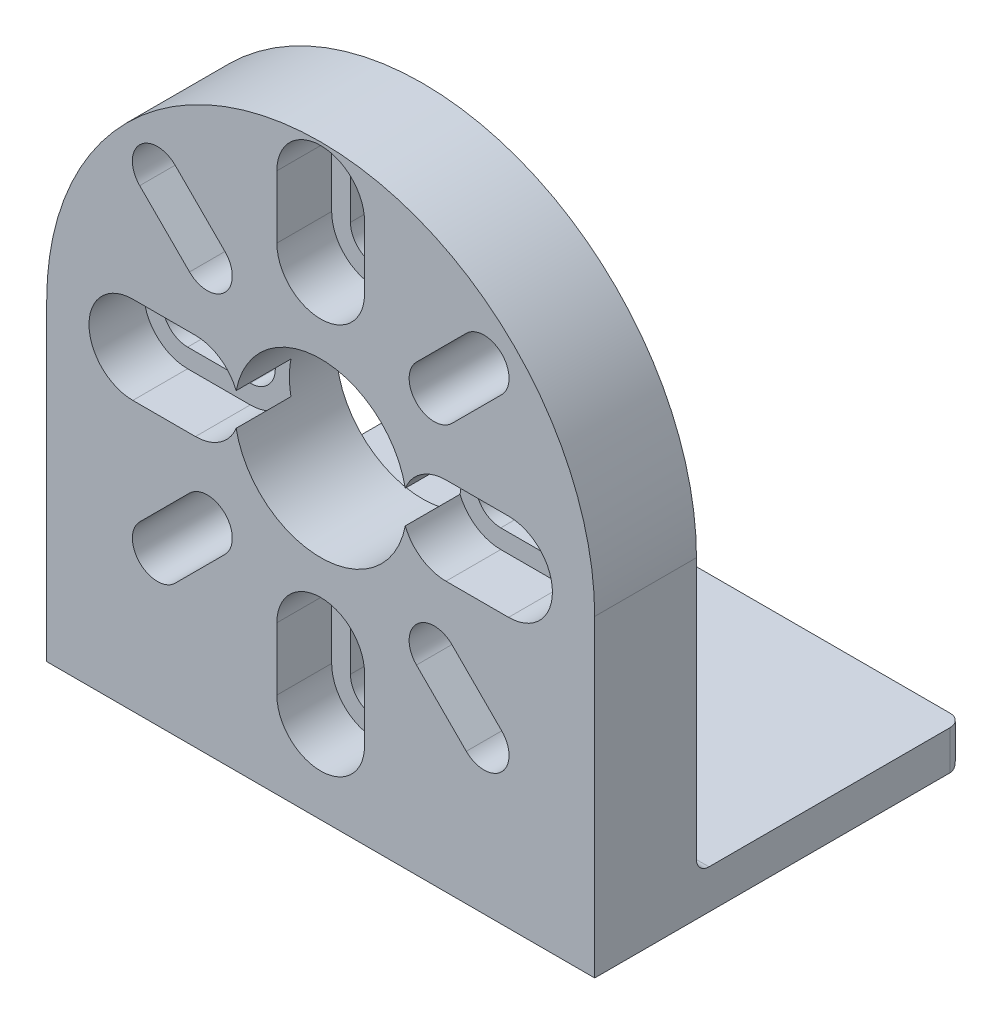
SolidWorks part; units mm, degrees
ref_plane "前视基准面" through (0, 0, 0) normal (0, 0, 1) x (1, 0, 0)
ref_plane "上视基准面" through (0, 0, 0) normal (0, 1, 0) x (1, 0, 0)
ref_plane "右视基准面" through (0, 0, 0) normal (1, 0, 0) x (0, 0, -1)
sketch "草图1" plane through (0, 0, 0) normal (0, 0, 1) x (1, 0, 0)
  line L0 (0, 0) -> (0, 8.1405) construction
  line L1 (0, 14.5) -> (0, 10.5) construction
  line L2 (6.9459, 0) -> (-5.9734, 0) construction
  line L3 (1.6, 14.5) -> (1.6, 10.5)
  line L4 (-1.6, 14.5) -> (-1.6, 10.5)
  line L5 (0, -14.5) -> (0, -10.5) construction
  line L6 (1.6, -14.5) -> (1.6, -10.5)
  line L7 (-1.6, -14.5) -> (-1.6, -10.5)
  line L8 (-12, 0) -> (-8, 0) construction
  line L11 (-12, 1.6) -> (-8, 1.6)
  line L14 (-12, -1.6) -> (-8, -1.6)
  line L15 (12, 0) -> (8, 0) construction
  line L16 (12, 1.6) -> (8, 1.6)
  line L17 (12, -1.6) -> (8, -1.6)
  arc A0 (1.6, 14.5) -> (-1.6, 14.5) centre (0, 14.5) ccw
  arc A1 (-1.6, 10.5) -> (1.6, 10.5) centre (0, 10.5) ccw
  arc A2 (1.6, -14.5) -> (-1.6, -14.5) centre (0, -14.5) cw
  arc A3 (-1.6, -10.5) -> (1.6, -10.5) centre (0, -10.5) cw
  arc A8 (-12, 1.6) -> (-12, -1.6) centre (-12, 0) ccw
  arc A9 (-8, -1.6) -> (-8, 1.6) centre (-8, 0) ccw
  arc A10 (12, 1.6) -> (12, -1.6) centre (12, 0) cw
  arc A11 (8, -1.6) -> (8, 1.6) centre (8, 0) cw
  circle A12 centre (0, 0) radius 17.5
  point P7 (0, 12.5)
  point P14 (0, -12.5)
  point P21 (-10, 0)
  point P28 (10, 0)
  dimension "D5" = 35
  dimension "D1" = 3.2
  dimension "D2" = 3.2
  dimension "D3" = 20
  dimension "D4" = 4
  dimension "D6" = 25
extrude "凸台-拉伸1" add sketch "草图1" along normal blind 3
sketch "草图2" plane through (0, 0, 3) normal (0, 0, 1) x (1, 0, 0)
  line L0 (0, 27.088) -> (0, -34.6752) construction
  line L1 (-17.5, -20) -> (17.5, -20)
  line L2 (29.4097, 0) -> (-37.8578, 0) construction
  line L3 (17.5, -20) -> (17.5, 0)
  line L4 (-17.5, -20) -> (-17.5, 0)
  circle A0 centre (0, 0) radius 17.5 construction
  arc A1 (-17.5, 0) -> (17.5, 0) centre (0, 0) ccw
  dimension "D1" = 20
  dimension "D2" = 35
extrude "凸台-拉伸2" add sketch "草图2" against normal blind 20
sketch "草图3" plane through (0, 0, -17) normal (0, 0, -1) x (-1, 0, 0)
  line L0 (20.2177, -17.5) -> (-21.8206, -17.5)
  line L1 (-21.8206, -17.5) -> (-21.8206, 0)
  line L2 (-21.8206, 0) -> (20.2177, 0)
  line L3 (20.2177, 0) -> (20.2177, -17.5)
  arc A0 (-17.5, 0) -> (17.5, 0) centre (0, 0) ccw construction
  arc A1 (-17.5, 0) -> (17.5, 0) centre (0, 0) ccw construction
extrude "切除-拉伸2" cut sketch "草图3" against normal up to surface (17 mm away) up to face at (-10, 0, 0)
fillet "圆角1" radius 0.8 4 edges at (0, -17.5, 0) (0, -20, -17) (-17.5, -18.75, -17) (17.5, -18.75, -17)
sketch "草图4" plane through (0, 0, 0) normal (0, 0, -1) x (-1, 0, 0)
  circle A0 centre (0, 0) radius 5.5
  dimension "D1" = 11
extrude "切除-拉伸3" cut sketch "草图4" against normal through all
sketch "草图5" plane through (0, 0, 3) normal (0, 0, 1) x (1, 0, 0)
  line L0 (1.6, -14.5) -> (1.6, -10.5) construction
  line L1 (-1.6, -10.5) -> (-1.6, -14.5) construction
  line L2 (-8, 1.6) -> (-12, 1.6) construction
  line L3 (-17.5, 0) -> (-17.5, -20)
  line L4 (-17.5, -20) -> (17.5, -20)
  line L5 (17.5, -20) -> (17.5, 0)
  line L6 (-17.5, 0) -> (-17.5, -20)
  line L7 (-17.5, -20) -> (17.5, -20)
  line L8 (17.5, -20) -> (17.5, 0)
  line L9 (-12, -1.6) -> (-8, -1.6) construction
  line L10 (8, -1.6) -> (12, -1.6) construction
  line L11 (12, 1.6) -> (8, 1.6) construction
  line L12 (1.6, 10.5) -> (1.6, 14.5) construction
  line L13 (-1.6, 14.5) -> (-1.6, 10.5) construction
  line L14 (1.6, -14.5) -> (1.6, -10.5)
  line L15 (-1.6, -10.5) -> (-1.6, -14.5)
  line L16 (-8, 1.6) -> (-12, 1.6)
  line L17 (-12, -1.6) -> (-8, -1.6)
  line L18 (8, -1.6) -> (12, -1.6)
  line L19 (12, 1.6) -> (8, 1.6)
  line L20 (1.6, 10.5) -> (1.6, 14.5)
  line L21 (-1.6, 14.5) -> (-1.6, 10.5)
  arc A0 (-1.6, -14.5) -> (1.6, -14.5) centre (0, -14.5) ccw construction
  arc A1 (17.5, 0) -> (-17.5, 0) centre (0, 0) ccw
  arc A2 (17.5, 0) -> (-17.5, 0) centre (0, 0) ccw
  arc A3 (1.6, -10.5) -> (-1.6, -10.5) centre (0, -10.5) ccw construction
  arc A4 (-12, 1.6) -> (-12, -1.6) centre (-12, 0) ccw construction
  arc A5 (-8, -1.6) -> (-8, 1.6) centre (-8, 0) ccw construction
  circle A6 centre (0, 0) radius 5.5 construction
  arc A7 (12, -1.6) -> (12, 1.6) centre (12, 0) ccw construction
  arc A8 (8, 1.6) -> (8, -1.6) centre (8, 0) ccw construction
  arc A9 (1.6, 14.5) -> (-1.6, 14.5) centre (0, 14.5) ccw construction
  arc A10 (-1.6, 10.5) -> (1.6, 10.5) centre (0, 10.5) ccw construction
  arc A11 (-1.6, -14.5) -> (1.6, -14.5) centre (0, -14.5) ccw
  arc A12 (1.6, -10.5) -> (-1.6, -10.5) centre (0, -10.5) ccw
  arc A13 (-12, 1.6) -> (-12, -1.6) centre (-12, 0) ccw
  arc A14 (-8, -1.6) -> (-8, 1.6) centre (-8, 0) ccw
  circle A15 centre (0, 0) radius 5.5
  arc A16 (12, -1.6) -> (12, 1.6) centre (12, 0) ccw
  arc A17 (8, 1.6) -> (8, -1.6) centre (8, 0) ccw
  arc A18 (1.6, 14.5) -> (-1.6, 14.5) centre (0, 14.5) ccw
  arc A19 (-1.6, 10.5) -> (1.6, 10.5) centre (0, 10.5) ccw
  dimension "D1" = 0
extrude "凸台-拉伸3" add sketch "草图5" along normal blind 3.5
sketch "草图6" plane through (0, 0, 6.5) normal (0, 0, 1) x (1, 0, 0)
  line L0 (-16.3, 0) -> (-16.3, -18.8)
  line L1 (-16.3, -18.8) -> (16.3, -18.8)
  line L2 (16.3, -18.8) -> (16.3, 0)
  line L3 (-17.5, 0) -> (-17.5, -20)
  line L4 (-17.5, -20) -> (17.5, -20)
  line L5 (17.5, -20) -> (17.5, 0)
  line L6 (-17.5, 0) -> (-17.5, -20) construction
  line L7 (-17.5, -20) -> (17.5, -20) construction
  line L8 (17.5, -20) -> (17.5, 0) construction
  arc A0 (16.3, 0) -> (-16.3, 0) centre (0, 0) ccw
  arc A1 (17.5, 0) -> (-17.5, 0) centre (0, 0) ccw
  arc A2 (17.5, 0) -> (-17.5, 0) centre (0, 0) ccw construction
  dimension "D1" = 0
  dimension "D2" = 1.2
extrude "切除-拉伸4" [suppressed] cut sketch "草图6" against normal blind 3.5
sketch "草图7" plane through (0, 0, 6.5) normal (0, 0, 1) x (1, 0, 0)
  line L0 (-12, -1.6) -> (-8, -1.6) construction
  line L1 (-8, 1.6) -> (-12, 1.6) construction
  line L2 (1.6, -14.5) -> (1.6, -10.5)
  line L3 (-1.6, -10.5) -> (-1.6, -14.5)
  line L4 (1.6, -14.5) -> (1.6, -10.5)
  line L5 (-1.6, -10.5) -> (-1.6, -14.5)
  line L6 (8, -1.6) -> (12, -1.6)
  line L7 (12, 1.6) -> (8, 1.6)
  line L8 (8, -1.6) -> (12, -1.6)
  line L9 (12, 1.6) -> (8, 1.6)
  line L10 (1.6, 10.5) -> (1.6, 14.5) construction
  line L11 (-1.6, 14.5) -> (-1.6, 10.5) construction
  line L12 (-12, -1.6) -> (-8, -1.6)
  line L13 (-8, 1.6) -> (-12, 1.6)
  line L14 (1.6, 10.5) -> (1.6, 14.5)
  line L15 (-1.6, 14.5) -> (-1.6, 10.5)
  line L16 (2.8, -14.5) -> (2.8, -10.5)
  line L17 (-2.8, -10.5) -> (-2.8, -14.5)
  line L18 (8, -2.8) -> (12, -2.8)
  line L19 (12, 2.8) -> (8, 2.8)
  line L20 (-12, -2.8) -> (-8, -2.8)
  line L21 (-8, 2.8) -> (-12, 2.8)
  line L22 (2.8, 10.5) -> (2.8, 14.5)
  line L23 (-2.8, 14.5) -> (-2.8, 10.5)
  arc A0 (-12, 1.6) -> (-12, -1.6) centre (-12, 0) ccw construction
  arc A1 (-8, -1.6) -> (-8, 1.6) centre (-8, 0) ccw construction
  arc A2 (-1.6, -14.5) -> (1.6, -14.5) centre (0, -14.5) ccw
  arc A3 (1.6, -10.5) -> (-1.6, -10.5) centre (0, -10.5) ccw
  arc A4 (-1.6, -14.5) -> (1.6, -14.5) centre (0, -14.5) ccw
  arc A5 (1.6, -10.5) -> (-1.6, -10.5) centre (0, -10.5) ccw
  arc A6 (8, 1.6) -> (8, -1.6) centre (8, 0) ccw
  arc A7 (12, -1.6) -> (12, 1.6) centre (12, 0) ccw
  arc A8 (8, 1.6) -> (8, -1.6) centre (8, 0) ccw
  arc A9 (12, -1.6) -> (12, 1.6) centre (12, 0) ccw
  arc A10 (-1.6, 10.5) -> (1.6, 10.5) centre (0, 10.5) ccw construction
  arc A11 (1.6, 14.5) -> (-1.6, 14.5) centre (0, 14.5) ccw construction
  arc A12 (-12, 1.6) -> (-12, -1.6) centre (-12, 0) ccw
  arc A13 (-8, -1.6) -> (-8, 1.6) centre (-8, 0) ccw
  arc A14 (-1.6, 10.5) -> (1.6, 10.5) centre (0, 10.5) ccw
  arc A15 (1.6, 14.5) -> (-1.6, 14.5) centre (0, 14.5) ccw
  arc A16 (2.8, -10.5) -> (-2.8, -10.5) centre (0, -10.5) ccw
  arc A17 (-2.8, -14.5) -> (2.8, -14.5) centre (0, -14.5) ccw
  arc A18 (12, -2.8) -> (12, 2.8) centre (12, 0) ccw
  arc A19 (8, 2.8) -> (8, -2.8) centre (8, 0) ccw
  arc A20 (-8, -2.8) -> (-8, 2.8) centre (-8, 0) ccw
  arc A21 (-12, 2.8) -> (-12, -2.8) centre (-12, 0) ccw
  arc A22 (2.8, 14.5) -> (-2.8, 14.5) centre (0, 14.5) ccw
  arc A23 (-2.8, 10.5) -> (2.8, 10.5) centre (0, 10.5) ccw
  dimension "D1" = 0
  dimension "D2" = 0
  dimension "D3" = 1.2
extrude "切除-拉伸5" cut sketch "草图7" against normal blind 3.5
sketch "草图8" plane through (0, 0, 6.5) normal (0, 0, 1) x (1, 0, 0)
  line L0 (0, 16.1) -> (0, 0) construction
  line L1 (0, 0) -> (13.6, 0) construction
  line L2 (13.6, 0) -> (0, 0) construction
  line L3 (0, 0) -> (7.7243, 7.7243) construction
  line L4 (0, 0) -> (7.76, -7.76) construction
  line L5 (10.4298, 10.4298) -> (7.2478, 7.2478) construction
  line L6 (11.5612, 9.2985) -> (8.3792, 6.1165)
  line L7 (9.2985, 11.5612) -> (6.1165, 8.3792)
  line L8 (-7.2478, 7.2478) -> (-10.4298, 10.4298) construction
  line L9 (-8.3792, 6.1165) -> (-11.5612, 9.2985)
  line L10 (-6.1165, 8.3792) -> (-9.2985, 11.5612)
  line L11 (7.2478, -7.2478) -> (10.4298, -10.4298) construction
  line L12 (6.1165, -8.3792) -> (9.2985, -11.5612)
  line L13 (8.3792, -6.1165) -> (11.5612, -9.2985)
  line L14 (-10.4298, -10.4298) -> (-7.2478, -7.2478) construction
  line L15 (-9.2985, -11.5612) -> (-6.1165, -8.3792)
  line L16 (-11.5612, -9.2985) -> (-8.3792, -6.1165)
  arc A0 (1.6, 14.5) -> (-1.6, 14.5) centre (0, 14.5) ccw construction
  arc A1 (12, -1.6) -> (12, 1.6) centre (12, 0) ccw construction
  arc A2 (11.5612, 9.2985) -> (9.2985, 11.5612) centre (10.4298, 10.4298) ccw
  arc A3 (6.1165, 8.3792) -> (8.3792, 6.1165) centre (7.2478, 7.2478) ccw
  arc A4 (-8.3792, 6.1165) -> (-6.1165, 8.3792) centre (-7.2478, 7.2478) ccw
  arc A5 (-9.2985, 11.5612) -> (-11.5612, 9.2985) centre (-10.4298, 10.4298) ccw
  arc A6 (6.1165, -8.3792) -> (8.3792, -6.1165) centre (7.2478, -7.2478) cw
  arc A7 (11.5612, -9.2985) -> (9.2985, -11.5612) centre (10.4298, -10.4298) cw
  arc A8 (-9.2985, -11.5612) -> (-11.5612, -9.2985) centre (-10.4298, -10.4298) cw
  arc A9 (-8.3792, -6.1165) -> (-6.1165, -8.3792) centre (-7.2478, -7.2478) cw
  point P11 (8.8388, 8.8388)
  point P21 (-8.8388, 8.8388)
  point P30 (8.8388, -8.8388)
  point P37 (-8.8388, -8.8388)
  point P42 (-8.4511, 8.4511)
  dimension "D1" = 45
  dimension "D2" = 90
  dimension "D3" = 3.2
  dimension "D4" = 4.5
  dimension "D5" = 25
  dimension "D6" = 25
extrude "切除-拉伸6" cut sketch "草图8" against normal up to surface (6.5 mm away) up to face at (-5.5, 0, 0)
equation "\"4.5.00mm\"=6"
